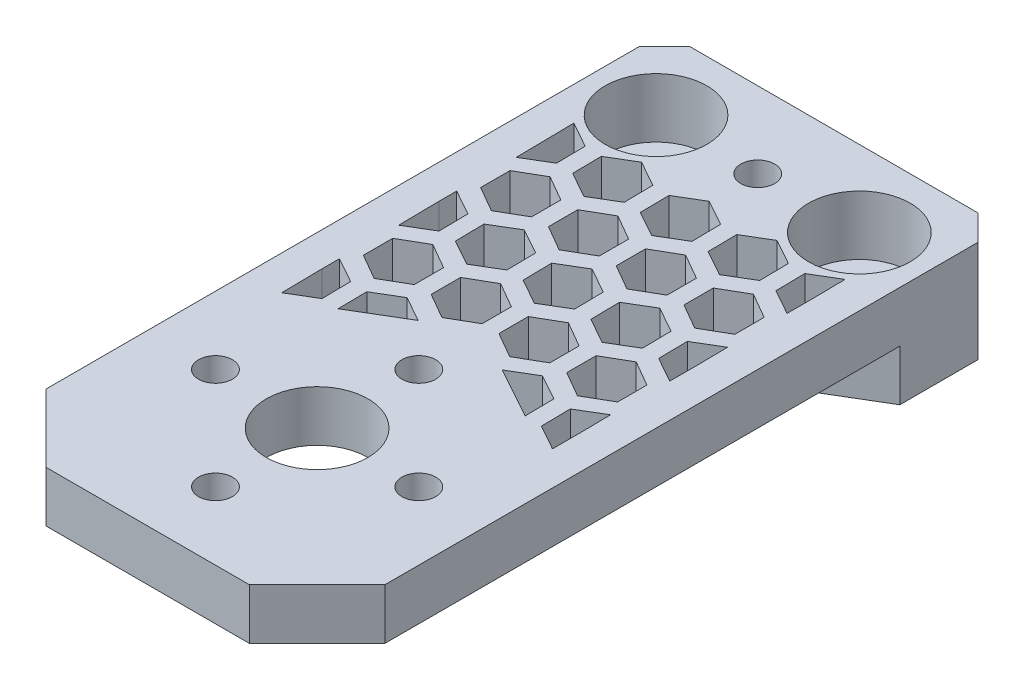
SolidWorks part; units mm, degrees
ref_plane "Front Plane" through (0, 0, 0) normal (0, 0, 1) x (1, 0, 0)
ref_plane "Top Plane" through (0, 0, 0) normal (0, 1, 0) x (1, 0, 0)
ref_plane "Right Plane" through (0, 0, 0) normal (1, 0, 0) x (0, 0, -1)
sketch "Sketch2" plane through (0, 0, 0) normal (0, 1, 0) x (1, 0, 0)
  line L0 (-23.3104, 0) -> (34.5451, 0) construction
  line L1 (-10, 34) -> (10, 34)
  line L2 (-10, 34) -> (-10, -10)
  line L3 (-10, -10) -> (10, -10)
  line L4 (10, 34) -> (10, -10)
  circle A0 centre (-6, 26) radius 1.5
  circle A1 centre (6, 26) radius 1.5
  circle A2 centre (0, 0) radius 3
  circle A3 centre (0, 26) radius 1
  circle A4 centre (-6, 0) radius 1
  circle A5 centre (0, 6) radius 1
  circle A6 centre (6, 0) radius 1
  circle A7 centre (0, -6) radius 1
  point P25 (0, 0)
  dimension "D1" = 26
  dimension "D2" = 26
  dimension "D3" = 3
  dimension "D4" = 3
  dimension "D5" = 26
  dimension "D6" = 2
  dimension "D7" = 20
  dimension "D8" = 10
  dimension "D9" = 8
  dimension "D10" = 10
  dimension "D11" = 6
  dimension "D12" = 2
  dimension "D13" = 4
  dimension "D14" = 6
extrude "Boss-Extrude1" add sketch "Sketch2" along normal blind 3
chamfer "Chamfer2" distance 4 angle 45 2 edges at (-10, 1.5, 10) (10, 1.5, 10)
sketch "Sketch5" plane through (0, 0, 0) normal (0, -1, 0) x (1, 0, 0)
  line L1 (10, 6) -> (10, -34) construction
  line L2 (-10, -34) -> (10, -34)
  line L3 (-10, -34) -> (-10, -22)
  line L4 (-10, -22) -> (10, -22)
  line L5 (10, -34) -> (10, -22)
  circle A0 centre (-6, -26) radius 1.5
  circle A1 centre (6, -26) radius 1.5
  dimension "D1" = 12
extrude "Boss-Extrude3" add sketch "Sketch5" along normal blind 3
chamfer "Chamfer3" distance 5 angle 45 2 edges at (10, 0, -34) (-10, 0, -34)
chamfer "Chamfer4" distance 3.5 angle 45 1 edges at (0, 3, -34)
chamfer "Chamfer5" distance 2 angle 45 2 edges
sketch "Sketch8" plane through (0, 0, -22) normal (0, 0, 1) x (1, 0, 0)
  line L0 (-6, 0) -> (-10, 0) construction
  line L1 (-8, 0) -> (8, 0)
  line L2 (-8, 0) -> (-8, -3)
  line L3 (-8, -3) -> (8, -3)
  line L4 (8, 0) -> (8, -3)
extrude "Boss-Extrude4" add sketch "Sketch8" along normal blind 3.5
sketch "Sketch9" plane through (8, 0, 0) normal (1, 0, 0) x (0, 0, -1)
  line L0 (18.5, 0) -> (22, -3)
  line L1 (22, -3) -> (18.5, -3)
  line L2 (18.5, 0) -> (18.5, -3)
extrude "Cut-Extrude14" cut sketch "Sketch9" against normal blind 20.5
sketch "Sketch6" plane through (0, 0, 0) normal (0, -1, 0) x (1, 0, 0)
  line L0 (-10, -21.1573) -> (10, -21.1573)
  line L1 (-10, -24) -> (-10, 6) construction
  line L2 (10, 6) -> (10, -24) construction
  line L3 (0, -7.8995) -> (0, -21.1573)
  line L4 (4.025, -12.7965) -> (2.5127, -13.6408)
  line L5 (-0.025, -16.2603) -> (1.4873, -15.416)
  line L6 (1.4873, -15.416) -> (1.5124, -13.6842)
  line L7 (1.5124, -13.6842) -> (0.025, -12.7965)
  line L8 (0.025, -12.7965) -> (-1.4873, -13.6408)
  line L9 (-1.4873, -13.6408) -> (-1.5124, -15.3726)
  line L10 (-1.5124, -15.3726) -> (-0.025, -16.2603)
  line L11 (5.5124, -13.6842) -> (4.025, -12.7965)
  line L12 (5.4873, -15.416) -> (5.5124, -13.6842)
  line L13 (3.975, -16.2603) -> (5.4873, -15.416)
  line L14 (2.4876, -15.3726) -> (3.975, -16.2603)
  line L15 (2.5127, -13.6408) -> (2.4876, -15.3726)
  line L16 (8.025, -12.7965) -> (6.5127, -13.6408)
  line L17 (-7.9651, -12.7809) -> (-8.0152, -16.2447)
  line L18 (-7.9651, -5.8765) -> (-8.0152, -9.3403)
  line L19 (8.025, -5.8609) -> (7.975, -9.3403)
  line L20 (6.4876, -15.3726) -> (7.975, -16.2603)
  line L21 (6.5127, -13.6408) -> (6.4876, -15.3726)
  line L22 (-3.97, -12.7965) -> (-5.4824, -13.6408)
  line L23 (-2.4827, -13.6842) -> (-3.97, -12.7965)
  line L24 (-2.5077, -15.416) -> (-2.4827, -13.6842)
  line L25 (-4.0201, -16.2603) -> (-2.5077, -15.416)
  line L26 (-5.5074, -15.3726) -> (-4.0201, -16.2603)
  line L27 (-5.4824, -13.6408) -> (-5.5074, -15.3726)
  line L28 (8.025, -12.7809) -> (7.975, -16.2447)
  line L29 (-6.4777, -13.6842) -> (-7.9651, -12.7965)
  line L30 (-6.5028, -15.416) -> (-6.4777, -13.6842)
  line L31 (-8.0152, -16.2603) -> (-6.5028, -15.416)
  line L32 (-7.9651, -19.7165) -> (-8.0152, -23.1647)
  line L33 (7.975, -23.1803) -> (8.025, -19.7009)
  line L34 (2.0275, -16.2563) -> (0.5275, -17.1224)
  line L35 (-1.9725, -19.7205) -> (-0.4725, -18.8544)
  line L36 (-0.4725, -18.8544) -> (-0.4725, -17.1224)
  line L37 (-0.4725, -17.1224) -> (-1.9725, -16.2563)
  line L38 (-1.9725, -16.2563) -> (-3.4725, -17.1224)
  line L39 (-3.4725, -17.1224) -> (-3.4725, -18.8544)
  line L40 (-3.4725, -18.8544) -> (-1.9725, -19.7205)
  line L41 (3.5275, -17.1224) -> (2.0275, -16.2563)
  line L42 (3.5275, -18.8544) -> (3.5275, -17.1224)
  line L43 (2.0275, -19.7205) -> (3.5275, -18.8544)
  line L44 (0.5275, -18.8544) -> (2.0275, -19.7205)
  line L45 (0.5275, -17.1224) -> (0.5275, -18.8544)
  line L46 (6.0275, -16.2563) -> (4.5275, -17.1224)
  line L47 (7.5275, -17.1224) -> (6.0275, -16.2563)
  line L48 (7.5275, -18.8544) -> (7.5275, -17.1224)
  line L49 (6.0275, -19.7205) -> (7.5275, -18.8544)
  line L50 (4.5275, -18.8544) -> (6.0275, -19.7205)
  line L51 (4.5275, -17.1224) -> (4.5275, -18.8544)
  line L52 (-1.9725, -16.2563) -> (-3.4725, -17.1224)
  line L53 (-0.4725, -17.1224) -> (-1.9725, -16.2563)
  line L54 (-0.4725, -18.8544) -> (-0.4725, -17.1224)
  line L55 (-1.9725, -19.7205) -> (-0.4725, -18.8544)
  line L56 (-3.4725, -18.8544) -> (-1.9725, -19.7205)
  line L57 (-3.4725, -17.1224) -> (-3.4725, -18.8544)
  line L58 (2.0275, -9.3363) -> (0.5275, -10.2024)
  line L59 (3.5275, -10.2024) -> (2.0275, -9.3363)
  line L60 (3.5275, -11.9344) -> (3.5275, -10.2024)
  line L61 (2.0275, -12.8005) -> (3.5275, -11.9344)
  line L62 (0.5275, -11.9344) -> (2.0275, -12.8005)
  line L63 (0.5275, -10.2024) -> (0.5275, -11.9344)
  line L64 (6.0275, -9.3363) -> (4.5275, -10.2024)
  line L65 (7.5275, -10.2024) -> (6.0275, -9.3363)
  line L66 (7.5275, -11.9344) -> (7.5275, -10.2024)
  line L67 (6.0275, -12.8005) -> (7.5275, -11.9344)
  line L68 (4.5275, -11.9344) -> (6.0275, -12.8005)
  line L69 (4.5275, -10.2024) -> (4.5275, -11.9344)
  line L70 (-5.4824, -6.7208) -> (-2.5077, -8.496)
  line L71 (2.4876, -8.4371) -> (5.5124, -6.7642)
  line L82 (-1.9725, -9.3363) -> (-3.4725, -10.2024)
  line L83 (-0.4725, -10.2024) -> (-1.9725, -9.3363)
  line L84 (-0.4725, -11.9344) -> (-0.4725, -10.2024)
  line L85 (-1.9725, -12.8005) -> (-0.4725, -11.9344)
  line L86 (-3.4725, -11.9344) -> (-1.9725, -12.8005)
  line L87 (-3.4725, -10.2024) -> (-3.4725, -11.9344)
  line L94 (-5.9725, -16.2563) -> (-7.4725, -17.1224)
  line L95 (-4.4725, -17.1224) -> (-5.9725, -16.2563)
  line L96 (-4.4725, -18.8544) -> (-4.4725, -17.1224)
  line L97 (-5.9725, -19.7205) -> (-4.4725, -18.8544)
  line L98 (-7.4725, -18.8544) -> (-5.9725, -19.7205)
  line L99 (-7.4725, -17.1224) -> (-7.4725, -18.8544)
  line L100 (-5.9725, -9.3363) -> (-7.4725, -10.2024)
  line L101 (-4.4725, -10.2024) -> (-5.9725, -9.3363)
  line L102 (-4.4725, -11.9344) -> (-4.4725, -10.2024)
  line L103 (-5.9725, -12.8005) -> (-4.4725, -11.9344)
  line L104 (-7.4725, -11.9344) -> (-5.9725, -12.8005)
  line L105 (-7.4725, -10.2024) -> (-7.4725, -11.9344)
  line L112 (-1.9725, -9.3363) -> (-3.4725, -10.2024)
  line L113 (-0.4725, -10.2024) -> (-1.9725, -9.3363)
  line L114 (-0.4725, -11.9344) -> (-0.4725, -10.2024)
  line L115 (-1.9725, -12.8005) -> (-0.4725, -11.9344)
  line L116 (-3.4725, -11.9344) -> (-1.9725, -12.8005)
  line L117 (-3.4725, -10.2024) -> (-3.4725, -11.9344)
  line L132 (5.4873, -8.496) -> (5.5124, -6.7642)
  line L133 (3.975, -9.3403) -> (5.4873, -8.496)
  line L134 (2.4876, -8.4526) -> (3.975, -9.3403)
  line L136 (8.025, -5.8765) -> (6.5127, -6.7208)
  line L140 (6.4876, -8.4526) -> (7.975, -9.3403)
  line L141 (6.5127, -6.7208) -> (6.4876, -8.4526)
  line L145 (-4.0201, -9.3403) -> (-2.5077, -8.496)
  line L146 (-5.5074, -8.4526) -> (-4.0201, -9.3403)
  line L147 (-5.4824, -6.7208) -> (-5.5074, -8.4526)
  line L149 (-6.4777, -6.7642) -> (-7.9651, -5.8765)
  line L150 (-6.5028, -8.496) -> (-6.4777, -6.7642)
  line L151 (-8.0152, -9.3403) -> (-6.5028, -8.496)
  line L162 (5.4873, -8.4804) -> (5.5124, -6.7486)
  line L163 (3.975, -9.3247) -> (5.4873, -8.4804)
  line L164 (2.4876, -8.4371) -> (3.975, -9.3247)
  line L166 (8.025, -5.8609) -> (6.5127, -6.7052)
  line L170 (6.4876, -8.4371) -> (7.975, -9.3247)
  line L171 (6.5127, -6.7052) -> (6.4876, -8.4371)
  line L172 (4.025, -12.7809) -> (2.5127, -13.6252)
  line L173 (-0.025, -16.2447) -> (1.4873, -15.4004)
  line L174 (1.4873, -15.4004) -> (1.5124, -13.6686)
  line L175 (1.5124, -13.6686) -> (0.025, -12.7809)
  line L176 (0.025, -12.7809) -> (-1.4873, -13.6252)
  line L177 (-1.4873, -13.6252) -> (-1.5124, -15.3571)
  line L178 (-1.5124, -15.3571) -> (-0.025, -16.2447)
  line L179 (5.5124, -13.6686) -> (4.025, -12.7809)
  line L180 (5.4873, -15.4004) -> (5.5124, -13.6686)
  line L181 (3.975, -16.2447) -> (5.4873, -15.4004)
  line L182 (2.4876, -15.3571) -> (3.975, -16.2447)
  line L183 (2.5127, -13.6252) -> (2.4876, -15.3571)
  line L184 (8.025, -12.7809) -> (6.5127, -13.6252)
  line L188 (6.4876, -15.3571) -> (7.975, -16.2447)
  line L189 (6.5127, -13.6252) -> (6.4876, -15.3571)
  line L190 (-3.97, -12.7809) -> (-5.4824, -13.6252)
  line L191 (-2.4827, -13.6686) -> (-3.97, -12.7809)
  line L192 (-2.5077, -15.4004) -> (-2.4827, -13.6686)
  line L193 (-4.0201, -16.2447) -> (-2.5077, -15.4004)
  line L194 (-5.5074, -15.3571) -> (-4.0201, -16.2447)
  line L195 (-5.4824, -13.6252) -> (-5.5074, -15.3571)
  line L197 (-6.4777, -13.6686) -> (-7.9651, -12.7809)
  line L198 (-6.5028, -15.4004) -> (-6.4777, -13.6686)
  line L199 (-8.0152, -16.2447) -> (-6.5028, -15.4004)
  line L205 (-4.0201, -9.3247) -> (-2.5077, -8.4804)
  line L206 (-5.5074, -8.4371) -> (-4.0201, -9.3247)
  line L207 (-5.4824, -6.7052) -> (-5.5074, -8.4371)
  line L209 (-6.4777, -6.7486) -> (-7.9651, -5.8609)
  line L210 (-6.5028, -8.4804) -> (-6.4777, -6.7486)
  line L211 (-8.0152, -9.3247) -> (-6.5028, -8.4804)
  line L214 (4.025, -19.7165) -> (2.5127, -20.5608)
  line L215 (-0.025, -23.1803) -> (1.4873, -22.336)
  line L216 (1.4873, -22.336) -> (1.5124, -20.6042)
  line L217 (1.5124, -20.6042) -> (0.025, -19.7165)
  line L218 (0.025, -19.7165) -> (-1.4873, -20.5608)
  line L219 (-1.4873, -20.5608) -> (-1.5124, -22.2926)
  line L220 (-1.5124, -22.2926) -> (-0.025, -23.1803)
  line L221 (5.5124, -20.6042) -> (4.025, -19.7165)
  line L222 (5.4873, -22.336) -> (5.5124, -20.6042)
  line L223 (3.975, -23.1803) -> (5.4873, -22.336)
  line L224 (2.4876, -22.2926) -> (3.975, -23.1803)
  line L225 (2.5127, -20.5608) -> (2.4876, -22.2926)
  line L226 (8.025, -19.7165) -> (6.5127, -20.5608)
  line L230 (6.4876, -22.2926) -> (7.975, -23.1803)
  line L231 (6.5127, -20.5608) -> (6.4876, -22.2926)
  line L232 (8, -21.1573) -> (8, 3.1716)
  line L235 (-8, -21.1573) -> (-8, 3.1716)
  line L237 (-3.97, -19.7165) -> (-5.4824, -20.5608)
  line L238 (-2.4827, -20.6042) -> (-3.97, -19.7165)
  line L239 (-2.5077, -22.336) -> (-2.4827, -20.6042)
  line L240 (-4.0201, -23.1803) -> (-2.5077, -22.336)
  line L241 (4.025, -19.7009) -> (2.5127, -20.5452) [skipped]
  line L242 (-0.025, -23.1647) -> (1.4873, -22.3204) [skipped]
  line L243 (1.4873, -22.3204) -> (1.5124, -20.5886) [skipped]
  line L244 (1.5124, -20.5886) -> (0.025, -19.7009) [skipped]
  line L245 (0.025, -19.7009) -> (-1.4873, -20.5452) [skipped]
  line L246 (-1.4873, -20.5452) -> (-1.5124, -22.2771) [skipped]
  line L247 (-1.5124, -22.2771) -> (-0.025, -23.1647) [skipped]
  line L248 (5.5124, -20.5886) -> (4.025, -19.7009) [skipped]
  line L249 (5.4873, -22.3204) -> (5.5124, -20.5886) [skipped]
  line L250 (3.975, -23.1647) -> (5.4873, -22.3204) [skipped]
  line L251 (2.4876, -22.2771) -> (3.975, -23.1647) [skipped]
  line L252 (2.5127, -20.5452) -> (2.4876, -22.2771) [skipped]
  line L253 (8.025, -19.7009) -> (6.5127, -20.5452) [skipped]
  line L257 (6.4876, -22.2771) -> (7.975, -23.1647) [skipped]
  line L258 (6.5127, -20.5452) -> (6.4876, -22.2771) [skipped]
  line L259 (-3.97, -19.7009) -> (-5.4824, -20.5452) [skipped]
  line L260 (-2.4827, -20.5886) -> (-3.97, -19.7009) [skipped]
  line L261 (-2.5077, -22.3204) -> (-2.4827, -20.5886) [skipped]
  line L262 (-4.0201, -23.1647) -> (-2.5077, -22.3204) [skipped]
  line L263 (-5.5074, -22.2771) -> (-4.0201, -23.1647) [skipped]
  line L264 (-5.4824, -20.5452) -> (-5.5074, -22.2771) [skipped]
  line L266 (-6.4777, -20.5886) -> (-7.9651, -19.7009) [skipped]
  line L267 (-6.5028, -22.3204) -> (-6.4777, -20.5886) [skipped]
  line L268 (-8.0152, -23.1647) -> (-6.5028, -22.3204) [skipped]
  line L271 (-5.5074, -22.2926) -> (-4.0201, -23.1803)
  line L272 (-5.4824, -20.5608) -> (-5.5074, -22.2926)
  line L274 (-6.4777, -20.6042) -> (-7.9651, -19.7165)
  line L275 (-6.5028, -22.336) -> (-6.4777, -20.6042)
  line L276 (-8.0152, -23.1803) -> (-6.5028, -22.336)
  line L279 (4.025, -19.7009) -> (2.5127, -20.5452)
  line L280 (-0.025, -23.1647) -> (1.4873, -22.3204)
  line L281 (1.4873, -22.3204) -> (1.5124, -20.5886)
  line L282 (1.5124, -20.5886) -> (0.025, -19.7009)
  line L283 (0.025, -19.7009) -> (-1.4873, -20.5452)
  line L284 (-1.4873, -20.5452) -> (-1.5124, -22.2771)
  line L285 (-1.5124, -22.2771) -> (-0.025, -23.1647)
  line L286 (5.5124, -20.5886) -> (4.025, -19.7009)
  line L287 (5.4873, -22.3204) -> (5.5124, -20.5886)
  line L288 (3.975, -23.1647) -> (5.4873, -22.3204)
  line L289 (2.4876, -22.2771) -> (3.975, -23.1647)
  line L290 (2.5127, -20.5452) -> (2.4876, -22.2771)
  line L291 (8.025, -19.7009) -> (6.5127, -20.5452)
  line L295 (6.4876, -22.2771) -> (7.975, -23.1647)
  line L296 (6.5127, -20.5452) -> (6.4876, -22.2771)
  line L297 (-3.97, -19.7009) -> (-5.4824, -20.5452)
  line L298 (-2.4827, -20.5886) -> (-3.97, -19.7009)
  line L299 (-2.5077, -22.3204) -> (-2.4827, -20.5886)
  line L300 (-4.0201, -23.1647) -> (-2.5077, -22.3204)
  line L301 (-5.5074, -22.2771) -> (-4.0201, -23.1647)
  line L302 (-5.4824, -20.5452) -> (-5.5074, -22.2771)
  line L303 (4.025, -5.8765) -> (2.5127, -6.7208) [skipped]
  line L304 (-0.025, -9.3403) -> (1.4873, -8.496) [skipped]
  line L305 (1.4873, -8.496) -> (1.5124, -6.7642) [skipped]
  line L306 (1.5124, -6.7642) -> (0.025, -5.8765) [skipped]
  line L307 (0.025, -5.8765) -> (-1.4873, -6.7208) [skipped]
  line L308 (-1.4873, -6.7208) -> (-1.5124, -8.4526) [skipped]
  line L309 (-1.5124, -8.4526) -> (-0.025, -9.3403) [skipped]
  line L310 (5.5124, -6.7642) -> (4.025, -5.8765) [skipped]
  line L311 (5.4873, -8.496) -> (5.5124, -6.7642) [skipped]
  line L312 (3.975, -9.3403) -> (5.4873, -8.496) [skipped]
  line L313 (2.4876, -8.4526) -> (3.975, -9.3403) [skipped]
  line L314 (2.5127, -6.7208) -> (2.4876, -8.4526) [skipped]
  line L315 (8.025, -5.8765) -> (6.5127, -6.7208) [skipped]
  line L319 (6.4876, -8.4526) -> (7.975, -9.3403) [skipped]
  line L320 (6.5127, -6.7208) -> (6.4876, -8.4526) [skipped]
  line L321 (-3.97, -5.8765) -> (-5.4824, -6.7208) [skipped]
  line L322 (-2.4827, -6.7642) -> (-3.97, -5.8765) [skipped]
  line L323 (-2.5077, -8.496) -> (-2.4827, -6.7642) [skipped]
  line L324 (-4.0201, -9.3403) -> (-2.5077, -8.496) [skipped]
  line L325 (-5.5074, -8.4526) -> (-4.0201, -9.3403) [skipped]
  line L326 (-5.4824, -6.7208) -> (-5.5074, -8.4526) [skipped]
  line L328 (-6.4777, -6.7642) -> (-7.9651, -5.8765) [skipped]
  line L329 (-6.5028, -8.496) -> (-6.4777, -6.7642) [skipped]
  line L330 (-8.0152, -9.3403) -> (-6.5028, -8.496) [skipped]
  line L334 (-6.4777, -20.5886) -> (-7.9651, -19.7009)
  line L335 (-6.5028, -22.3204) -> (-6.4777, -20.5886)
  line L336 (-8.0152, -23.1647) -> (-6.5028, -22.3204)
  line L369 (-5.9568, -16.2563) -> (-7.4568, -17.1224) [skipped]
  line L370 (-4.4568, -17.1224) -> (-5.9568, -16.2563) [skipped]
  line L371 (-4.4568, -18.8544) -> (-4.4568, -17.1224) [skipped]
  line L372 (-5.9568, -19.7205) -> (-4.4568, -18.8544) [skipped]
  line L373 (-7.4568, -18.8544) -> (-5.9568, -19.7205) [skipped]
  line L374 (-7.4568, -17.1224) -> (-7.4568, -18.8544) [skipped]
  line L375 (2.0118, -16.2563) -> (0.5118, -17.1224) [skipped]
  line L376 (0.5118, -17.1224) -> (0.5118, -18.8544) [skipped]
  line L377 (2.0118, -16.2563) -> (0.5118, -17.1224) [skipped]
  line L378 (3.5118, -18.8544) -> (3.5118, -17.1224) [skipped]
  line L379 (2.0118, -19.7205) -> (3.5118, -18.8544) [skipped]
  line L380 (0.5118, -18.8544) -> (2.0118, -19.7205) [skipped]
  line L381 (7.4962, -18.8544) -> (7.4962, -17.1224) [skipped]
  line L382 (5.9962, -19.7205) -> (7.4962, -18.8544) [skipped]
  line L383 (4.4962, -18.8544) -> (5.9962, -19.7205) [skipped]
  line L384 (4.4962, -17.1224) -> (4.4962, -18.8544) [skipped]
  line L385 (3.5118, -18.8544) -> (3.5118, -17.1224) [skipped]
  line L386 (2.0118, -19.7205) -> (3.5118, -18.8544) [skipped]
  line L387 (0.5118, -18.8544) -> (2.0118, -19.7205) [skipped]
  line L388 (0.5118, -17.1224) -> (0.5118, -18.8544) [skipped]
  line L389 (3.5118, -17.1224) -> (2.0118, -16.2563) [skipped]
  line L390 (5.9962, -16.2563) -> (4.4962, -17.1224) [skipped]
  line L391 (7.4962, -17.1224) -> (5.9962, -16.2563) [skipped]
  line L392 (3.5118, -17.1224) -> (2.0118, -16.2563) [skipped]
  line L398 (-7.9651, -12.7965) -> (-9.4774, -13.6408) [skipped]
  line L399 (-9.5025, -15.3726) -> (-8.0152, -16.2603) [skipped]
  line L400 (-9.4774, -13.6408) -> (-9.5025, -15.3726) [skipped]
  line L401 (9.5124, -13.6842) -> (8.025, -12.7965) [skipped]
  line L402 (9.4873, -15.416) -> (9.5124, -13.6842) [skipped]
  line L403 (7.975, -16.2603) -> (9.4873, -15.416) [skipped]
  line L407 (2.0275, -2.4163) -> (0.5275, -3.2824) [skipped]
  line L408 (3.5275, -3.2824) -> (2.0275, -2.4163) [skipped]
  line L409 (3.5275, -5.0144) -> (3.5275, -3.2824) [skipped]
  line L410 (0.5275, -3.2824) -> (0.5275, -5.0144) [skipped]
  line L411 (6.0275, -2.4163) -> (4.5275, -3.2824) [skipped]
  line L412 (7.5275, -3.2824) -> (6.0275, -2.4163) [skipped]
  line L413 (7.5275, -5.0144) -> (7.5275, -3.2824) [skipped]
  line L414 (4.5275, -3.2824) -> (4.5275, -5.0144) [skipped]
  line L415 (-1.9725, -2.4163) -> (-3.4725, -3.2824) [skipped]
  line L416 (-0.4725, -3.2824) -> (-1.9725, -2.4163) [skipped]
  line L417 (-0.4725, -5.0144) -> (-0.4725, -3.2824) [skipped]
  line L418 (-3.4725, -3.2824) -> (-3.4725, -5.0144) [skipped]
  line L419 (-5.9725, -2.4163) -> (-7.4725, -3.2824) [skipped]
  line L420 (-4.4725, -3.2824) -> (-5.9725, -2.4163) [skipped]
  line L421 (-4.4725, -5.0144) -> (-4.4725, -3.2824) [skipped]
  line L422 (-7.4725, -3.2824) -> (-7.4725, -5.0144) [skipped]
  line L423 (-1.9725, -2.4163) -> (-3.4725, -3.2824) [skipped]
  line L424 (-0.4725, -3.2824) -> (-1.9725, -2.4163) [skipped]
  line L425 (-0.4725, -5.0144) -> (-0.4725, -3.2824) [skipped]
  line L426 (-3.4725, -3.2824) -> (-3.4725, -5.0144) [skipped]
  line L427 (2.0275, -5.8805) -> (3.5275, -5.0144) [skipped]
  line L428 (0.5275, -5.0144) -> (2.0275, -5.8805) [skipped]
  line L429 (6.0275, -5.8805) -> (7.5275, -5.0144) [skipped]
  line L430 (4.5275, -5.0144) -> (6.0275, -5.8805) [skipped]
  line L431 (-1.9725, -5.8805) -> (-0.4725, -5.0144) [skipped]
  line L432 (-3.4725, -5.0144) -> (-1.9725, -5.8805) [skipped]
  line L433 (-5.9725, -5.8805) -> (-4.4725, -5.0144) [skipped]
  line L434 (-7.4725, -5.0144) -> (-5.9725, -5.8805) [skipped]
  line L435 (-1.9725, -5.8805) -> (-0.4725, -5.0144) [skipped]
  line L436 (-3.4725, -5.0144) -> (-1.9725, -5.8805) [skipped]
  line L437 (-0.025, -9.3403) -> (1.4873, -8.496) [skipped]
  line L438 (1.4873, -8.496) -> (1.5124, -6.7642) [skipped]
  line L439 (1.5124, -6.7642) -> (0.025, -5.8765) [skipped]
  line L440 (0.025, -5.8765) -> (-1.4873, -6.7208) [skipped]
  line L441 (-1.4873, -6.7208) -> (-1.5124, -8.4526) [skipped]
  line L442 (-1.5124, -8.4526) -> (-0.025, -9.3403) [skipped]
  line L443 (-0.025, -9.3247) -> (1.4873, -8.4804) [skipped]
  line L444 (1.4873, -8.4804) -> (1.5124, -6.7486) [skipped]
  line L445 (1.5124, -6.7486) -> (0.025, -5.8609) [skipped]
  line L446 (0.025, -5.8609) -> (-1.4873, -6.7052) [skipped]
  line L447 (-1.4873, -6.7052) -> (-1.5124, -8.4371) [skipped]
  line L448 (-1.5124, -8.4371) -> (-0.025, -9.3247) [skipped]
  line L449 (-2.4827, -6.7642) -> (-3.97, -5.8765) [skipped]
  line L450 (-3.97, -5.8765) -> (-5.4824, -6.7208) [skipped]
  line L451 (-2.4827, -6.7486) -> (-3.97, -5.8609) [skipped]
  line L452 (-3.97, -5.8609) -> (-5.4824, -6.7052) [skipped]
  line L453 (2.5127, -6.7208) -> (2.4876, -8.4526) [skipped]
  line L454 (-2.5077, -8.496) -> (-2.4827, -6.7642) [skipped]
  line L455 (2.5127, -6.7052) -> (2.4876, -8.4371) [skipped]
  line L456 (-2.5077, -8.4804) -> (-2.4827, -6.7486) [skipped]
  line L457 (4.025, -5.8765) -> (2.5127, -6.7208) [skipped]
  line L458 (5.5124, -6.7642) -> (4.025, -5.8765) [skipped]
  line L459 (4.025, -5.8609) -> (2.5127, -6.7052) [skipped]
  line L460 (5.5124, -6.7486) -> (4.025, -5.8609) [skipped]
  circle A1 centre (0, -14.5284) radius 1.5 construction
  circle A2 centre (-1.9725, -17.9884) radius 1.5 construction
  dimension "D1" = 3
  dimension "D4" = 3
  dimension "D5" = 60
  dimension "D9" = 60
  dimension "D13" = 3
  dimension "D16" = 3
  dimension "D6" = 60
  dimension "D12" = 2
  dimension "D2" = 3
  dimension "D3" = 3
  dimension "D7" = 3
  dimension "D8" = 2
  dimension "D10" = 2
  dimension "D11" = 2
  dimension "D14" = 2
  dimension "D15" = 2
extrude "Cut-Extrude12" cut sketch "Sketch6" against normal blind 3.5 and the other way blind 20.5
sketch "Sketch7" plane through (0, 3, 0) normal (0, 1, 0) x (1, 0, 0)
  circle A0 centre (-6, 26) radius 3
  circle A1 centre (6, 26) radius 3
  dimension "D1" = 6
  dimension "D2" = 6
extrude "Cut-Extrude13" cut sketch "Sketch7" against normal blind 3.5
sketch "Sketch10" plane through (0, 0, 0) normal (0, -1, 0) x (1, 0, 0)
  line L0 (-8.0152, -23.1647) -> (-10.7509, -24.6919)
  line L1 (-10.7509, -24.6919) -> (-10.7509, -21.7931)
  line L2 (-7.6927, -21.7931) -> (-7.9651, -19.7165)
  line L3 (-7.6927, -21.7931) -> (-8.0152, -23.1647)
  line L5 (-7.9651, -19.7165) -> (-10.7509, -19.7165)
  line L6 (-10.7509, -21.7931) -> (-10.7509, -19.7165)
  line L7 (7.975, -23.1803) -> (10.4355, -24.6487)
  line L8 (10.4355, -24.6487) -> (10.4355, -19.3133)
  line L9 (10.4355, -19.3133) -> (8, -19.7305)
  line L10 (8, -19.7305) -> (7.3298, -21.0158)
  line L11 (7.3298, -21.0158) -> (7.975, -23.1803)
extrude "Cut-Extrude15" cut sketch "Sketch10" along normal blind 8.5
sketch "Sketch11" plane through (0, -3, 0) normal (0, -1, 0) x (1, 0, 0)
  circle A0 centre (-6, -26) radius 2.4
  circle A1 centre (6, -26) radius 2.4
  circle A2 centre (-6, -26) radius 1.5
  circle A3 centre (6, -26) radius 1.5
  dimension "D1" = 4.8
  dimension "D2" = 4.8
extrude "Boss-Extrude5" add sketch "Sketch11" along normal blind 0.55
